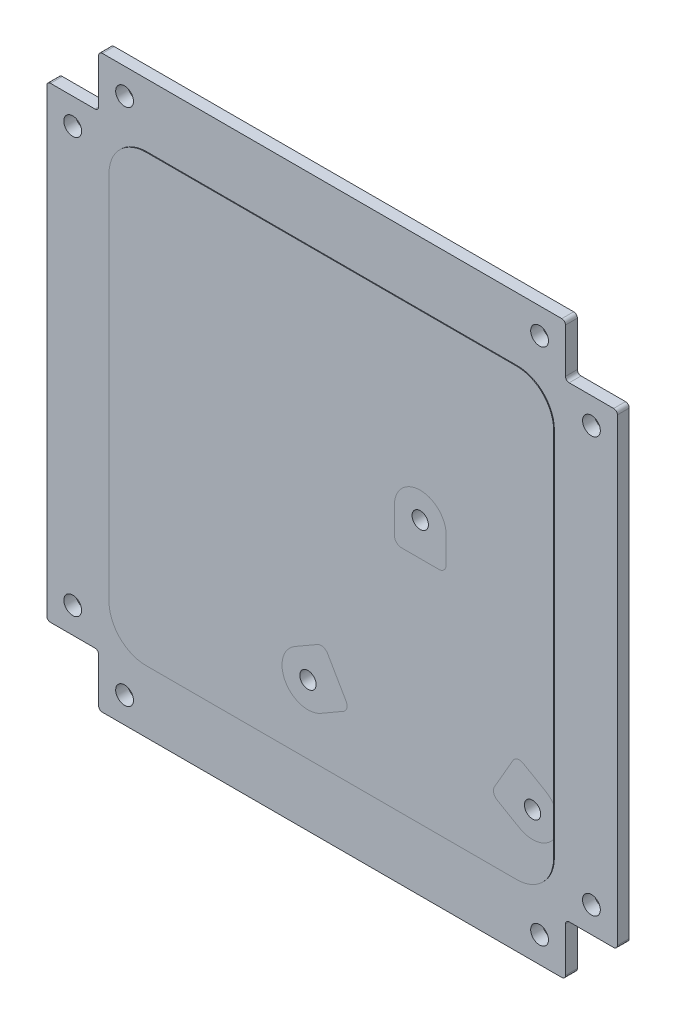
SolidWorks part; units mm, degrees
material "PET"
ref_plane "Front Plane" through (0, 0, 0) normal (0, 0, 1) x (1, 0, 0)
ref_plane "Top Plane" through (0, 0, 0) normal (0, 1, 0) x (1, 0, 0)
ref_plane "Right Plane" through (0, 0, 0) normal (1, 0, 0) x (0, 0, -1)
sketch "Sketch1" plane through (0, 0, 0) normal (0, 0, 1) x (1, 0, 0)
  line L0 (-31.5, 38) -> (-31.5, 32)
  line L1 (-31, -38.5) -> (31, -38.5)
  line L2 (-38.5, 31) -> (-38.5, -31)
  line L3 (-31, 38.5) -> (31, 38.5)
  line L4 (38.5, -31) -> (38.5, 31)
  line L5 (31.5, -38) -> (31.5, -32)
  line L6 (32, -31.5) -> (38, -31.5)
  line L7 (-32, 31.5) -> (-38, 31.5)
  line L8 (31.5, 38) -> (31.5, 32)
  line L9 (32, 31.5) -> (38, 31.5)
  line L10 (-38, -31.5) -> (-32, -31.5)
  line L11 (-31.5, -32) -> (-31.5, -38)
  line L12 (-32, -32) -> (32, 32) construction
  line L13 (32, -32) -> (-32, 32) construction
  arc A0 (-31, 38.5) -> (-31.5, 38) centre (-31, 38) ccw
  arc A1 (31, 38.5) -> (31.5, 38) centre (31, 38) cw
  arc A2 (31.5, 32) -> (32, 31.5) centre (32, 32) ccw
  arc A3 (38, 31.5) -> (38.5, 31) centre (38, 31) cw
  arc A4 (31, -38.5) -> (31.5, -38) centre (31, -38) ccw
  arc A5 (32, -31.5) -> (31.5, -32) centre (32, -32) ccw
  arc A6 (38, -31.5) -> (38.5, -31) centre (38, -31) ccw
  arc A7 (-31.5, -38) -> (-31, -38.5) centre (-31, -38) ccw
  arc A8 (-31.5, -32) -> (-32, -31.5) centre (-32, -32) ccw
  arc A9 (-38.5, -31) -> (-38, -31.5) centre (-38, -31) ccw
  arc A10 (-38, 31.5) -> (-38.5, 31) centre (-38, 31) ccw
  arc A11 (-32, 31.5) -> (-31.5, 32) centre (-32, 32) ccw
  point P0 (0, 0)
  dimension "D4" = 0.5
  dimension "D1" = 7
  dimension "D2" = 7
  dimension "D3" = 7
  dimension "D5" = 7
  dimension "D6" = 7
  dimension "D7" = 7
  dimension "D8" = 7
  dimension "D9" = 7
  dimension "D10" = 77
  dimension "D11" = 77
extrude "Boss-Extrude1" add sketch "Sketch1" along normal blind 1.6
sketch "Esboço1" plane through (0, 0, 1.6) normal (0, 0, 1) x (1, 0, 0)
  line L1 (-25, -30) -> (25, -30)
  line L2 (-30, -25) -> (-30, 25)
  line L3 (-25, 30) -> (25, 30)
  line L4 (30, -25) -> (30, 25)
  line L5 (-25, -25) -> (25, 25) construction
  line L6 (-25, 25) -> (25, -25) construction
  arc A0 (-30, 25) -> (-25, 30) centre (-25, 25) cw
  arc A1 (25, 30) -> (30, 25) centre (25, 25) cw
  arc A2 (30, -25) -> (25, -30) centre (25, -25) cw
  arc A3 (-25, -30) -> (-30, -25) centre (-25, -25) cw
  point P0 (0, 0)
  dimension "D1" = 5
  dimension "D2" = 60
  dimension "D3" = 60
extrude "Boss-Extrude2" add sketch "Esboço1" along normal blind 0.1
hole_wizard "M2 Hole1-FixingStructure" positions "Sketch3" profile "Sketch2" hole size "M2" standard "DIN"
sketch "Sketch3" plane through (0, 0, 0) normal (0, 0, -1) x (-1, 0, 0)
  line L0 (-31, 38.5) -> (31, 38.5) construction
  line L1 (31, -38.5) -> (-31, -38.5) construction
  line L2 (-38.5, -31) -> (-38.5, 31) construction
  line L3 (38.5, 31) -> (38.5, -31) construction
  line L4 (-31, 38.5) -> (31, 38.5) construction
  line L5 (31, -38.5) -> (-31, -38.5) construction
  line L6 (38.5, 31) -> (38.5, -31) construction
  line L7 (-38.5, -31) -> (-38.5, 31) construction
  point P0 (-28, 35)
  point P2 (28, 35)
  point P4 (-28, -35)
  point P6 (28, -35)
  point P20 (35, 28)
  point P22 (35, -28)
  point P24 (-35, -28)
  point P26 (-35, 28)
  dimension "D1" = 3.5
  dimension "D2" = 3.5
  dimension "D3" = 10.5
  dimension "D4" = 10.5
  dimension "D5" = 10.5
  dimension "D6" = 10.5
  dimension "D7" = 3.5
  dimension "D8" = 3.5
sketch "Sketch2" plane through (28, 35, 0) normal (1, 0, 0) x (0, 1, 0)
  line L0 (0, 0) -> (0, 200.721)
  line L1 (0, 200.721) -> (1.2, 200)
  line L2 (1.2, 200) -> (1.2, 0)
  line L5 (1.2, 0) -> (0, 0)
  line L10 (0, 200.721) -> (-1.2, 200) construction
  line L11 (0, -6.35) -> (0, 107.95) construction
  dimension "Hole Dia." = 2.4
  dimension "Hole Depth" = 200
  dimension "Drill Angle" = 118
sketch "Sketch4" plane through (0, 0, 1.7) normal (0, 0, 1) x (1, 0, 0)
  line L5 (15.5, 5.5) -> (15.5, 2)
  line L6 (-4.9054, -17.7189) -> (-2.7404, -16.4689)
  line L7 (0.7596, -22.5311) -> (-1.4054, -23.7811)
  line L8 (-4.9054, -17.7189) -> (-1.8744, -15.9689)
  line L9 (1.6256, -22.0311) -> (-1.4054, -23.7811)
  line L10 (-0.5083, -16.3349) -> (1.9917, -20.6651)
  line L11 (-0.5083, -16.3349) -> (1.9917, -20.6651)
  line L12 (8.5, 2) -> (8.5, 5.5)
  line L13 (14.5, 1) -> (9.5, 1)
  line L14 (25.4054, -23.7811) -> (22.3744, -22.0311)
  line L15 (25.8744, -15.9689) -> (28.9054, -17.7189)
  line L16 (22.0083, -20.6651) -> (24.5083, -16.3349)
  arc A2 (1.6256, -22.0311) -> (1.9917, -20.6651) centre (1.1256, -21.1651) ccw
  arc A3 (-4.9054, -17.7189) -> (-1.4054, -23.7811) centre (-3.1554, -20.75) ccw
  arc A4 (-4.9054, -17.7189) -> (-1.4054, -23.7811) centre (-3.1554, -20.75) ccw
  arc A5 (-1.8744, -15.9689) -> (-0.5083, -16.3349) centre (-1.3744, -16.8349) cw
  circle A6 centre (12, -12) radius 10 construction
  arc A7 (8.5, 2) -> (9.5, 1) centre (9.5, 2) ccw
  arc A8 (15.5, 5.5) -> (8.5, 5.5) centre (12, 5.5) ccw
  arc A9 (15.5, 2) -> (14.5, 1) centre (14.5, 2) cw
  arc A10 (25.8744, -15.9689) -> (24.5083, -16.3349) centre (25.3744, -16.8349) ccw
  arc A11 (25.4054, -23.7811) -> (28.9054, -17.7189) centre (27.1554, -20.75) ccw
  arc A12 (22.3744, -22.0311) -> (22.0083, -20.6651) centre (22.8744, -21.1651) cw
  point P13 (12, -12)
  point P37 (12, -12)
  dimension "D3" = 1
  dimension "D1" = 1
  dimension "D2" = 1
  dimension "D4" = 3
split line "Split Line1"
sketch "Sketch5" plane through (0, 0, 1.7) normal (0, 0, 1) x (1, 0, 0)
  circle A0 centre (-3.1554, -20.75) radius 1.1 construction
  circle A1 centre (27.1554, -20.75) radius 1.1 construction
  circle A2 centre (12, 5.5) radius 1.1 construction
  circle A3 centre (-3.1554, -20.75) radius 1.1
  circle A4 centre (27.1554, -20.75) radius 1.1
  circle A5 centre (12, 5.5) radius 1.1
extrude "Cut-Extrude1" cut sketch "Sketch5" against normal up to surface (1.7 mm away) up to face at (26.8, 35, 0)
